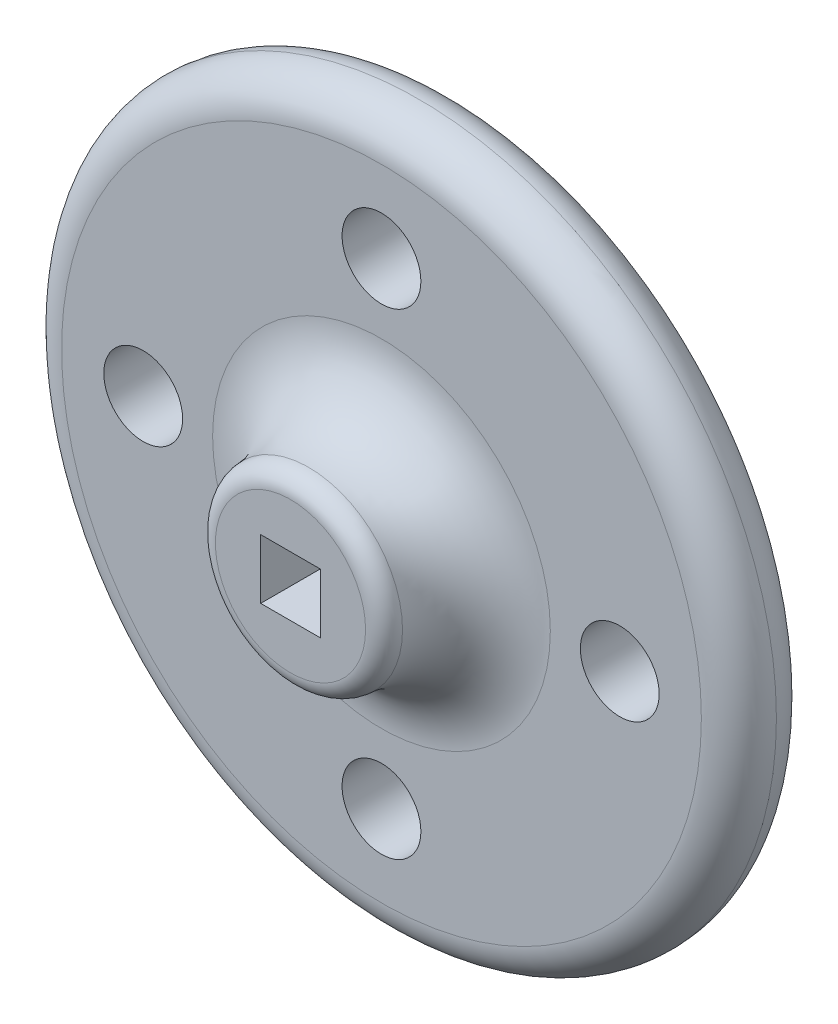
SolidWorks part; units mm, degrees
ref_plane "Front Plane" through (0, 0, 0) normal (0, 0, 1) x (1, 0, 0)
ref_plane "Top Plane" through (0, 0, 0) normal (0, 1, 0) x (1, 0, 0)
ref_plane "Right Plane" through (0, 0, 0) normal (1, 0, 0) x (0, 0, -1)
sketch "Sketch1" plane through (0, 0, 0) normal (0, 0, 1) x (1, 0, 0)
  line L1 (1.5875, 1.5875) -> (-1.5875, 1.5875)
  line L2 (1.5875, 1.5875) -> (1.5875, -1.5875)
  line L3 (1.5875, -1.5875) -> (-1.5875, -1.5875)
  line L4 (-1.5875, 1.5875) -> (-1.5875, -1.5875)
  line L5 (1.5875, 1.5875) -> (-1.5875, -1.5875) construction
  line L6 (1.5875, -1.5875) -> (-1.5875, 1.5875) construction
  circle A1 centre (12.7, 0) radius 2.1
  circle A2 centre (0, -12.7) radius 2.1
  circle A3 centre (-12.7, 0) radius 2.1
  circle A4 centre (0, 12.7) radius 2.1
  circle A5 centre (0, 0) radius 19.05
  circle A6 centre (0, 0) radius 5
  point P0 (0, 0)
  dimension "D2" = 4.2
  dimension "D5" = 38.1
  dimension "D6" = 10
  dimension "D1" = 3.175
  dimension "D3" = 12.7
  dimension "D4" = 4
extrude "Boss-Extrude1" add sketch "Sketch1" along normal blind 4 contours A5 A6 A1 A2 A3 A4 | A6 L4 L1 L2 L3 region at (-18.5112, 0, 0) region at (-4.8586, 0, 0)
extrude "Boss-Extrude2" add sketch "Sketch1<3>" along normal blind 4.85 from surface contours A6 L4 L1 L2 L3 region at (-4.8586, 0, 0) starting at face at (14.8, 0, 4)
sketch "Sketch1<3>" plane through (0, 0, 0) normal (0, 0, 1) x (1, 0, 0) same geometry as "Sketch1"
fillet "Fillet1" radius 4 1 edges at (5, 0, 4)
fillet "Fillet2" radius 1 1 edges at (5, 0, 8.85)
fillet "Fillet3" radius 2 2 edges at (19.05, 0, 0) (19.05, 0, 4)
